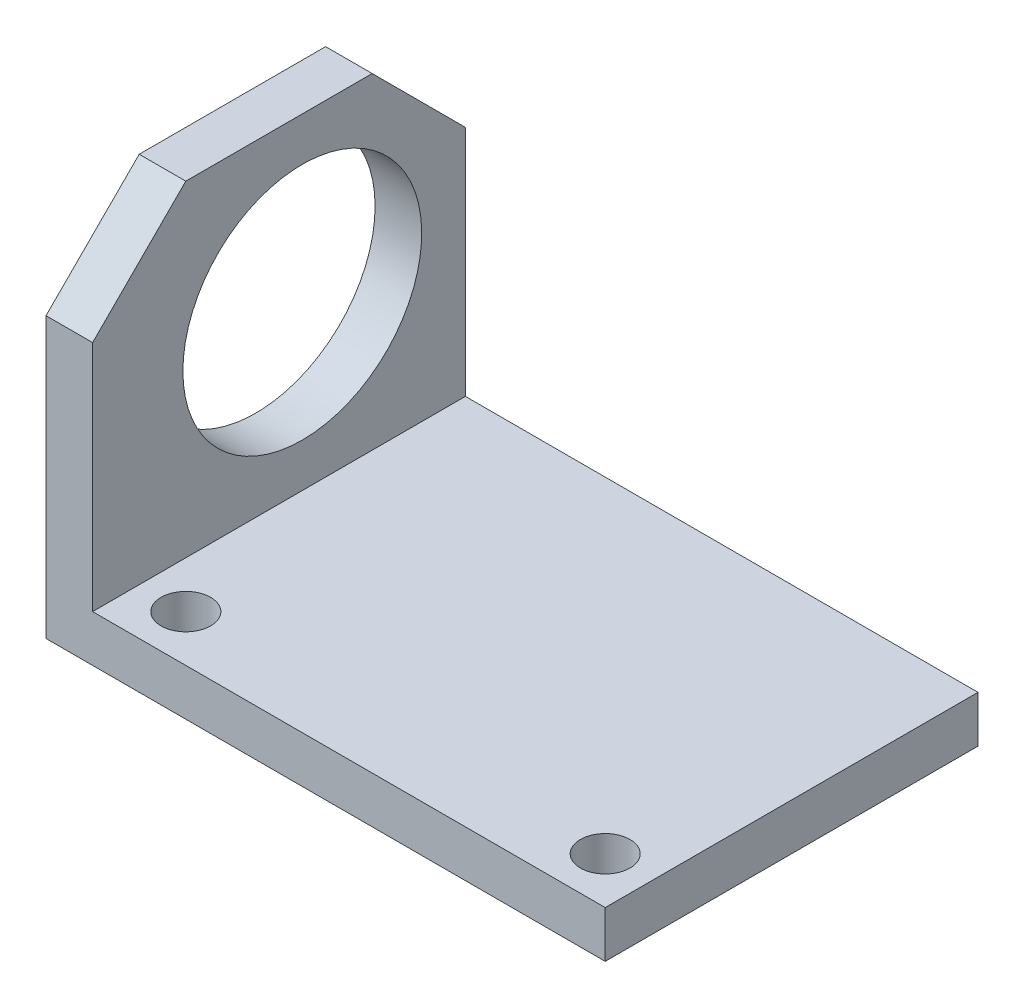
SolidWorks part; units mm, degrees
ref_plane "Front" through (0, 0, 0) normal (0, 0, 1) x (1, 0, 0)
ref_plane "Top" through (0, 0, 0) normal (0, 1, 0) x (1, 0, 0)
ref_plane "Right" through (0, 0, 0) normal (1, 0, 0) x (0, 0, -1)
sketch "Sketch1" plane through (0, 0, 0) normal (0, 0, 1) x (1, 0, 0)
  line L0 (0, 0) -> (76.2, 0)
  line L1 (50, 0) -> (-50, 0) construction
  line L2 (76.2, 0) -> (76.2, 6.35)
  line L3 (76.2, 6.35) -> (6.35, 6.35)
  line L4 (6.35, 6.35) -> (6.35, 50.8)
  line L5 (6.35, 50.8) -> (0, 50.8)
  line L6 (0, -50) -> (0, 50) construction
  line L7 (0, 50.8) -> (0, 0)
  dimension "D1" = 6.35
  dimension "D2" = 76.2
  dimension "D3" = 50.8
extrude "Boss-Extrude1" add sketch "Sketch1" along normal mid plane 50.8
sketch "Sketch2" plane through (0, 0, 0) normal (0, -1, 0) x (1, 0, 0)
  line L0 (76.2, 19.05) -> (69.85, 19.05) construction
  line L2 (69.85, 19.05) -> (12.7, 19.05) construction
  line L3 (76.2, 25.4) -> (76.2, -25.4) construction
  line L4 (0, 25.4) -> (76.2, 25.4) construction
  dimension "D1" = 57.15
  dimension "D2" = 6.35
  dimension "D3" = 6.35
hole_wizard "1/4 Clearance Hole1" positions "Sketch4" profile "Sketch3" hole size "1/4" standard "ANSI Inch" end condition through all
sketch "Sketch4" plane through (0, 0, 0) normal (0, -1, 0) x (-1, 0, 0)
  point P0 (-12.7, -19.05)
  point P3 (-69.85, -19.05)
sketch "Sketch3" plane through (12.7, 0, 19.05) normal (1, 0, 0) x (0, 0, -1)
  line L0 (0, 0) -> (0, 50.8)
  line L1 (0, 50.8) -> (3.3782, 50.8)
  line L2 (3.3782, 50.8) -> (3.3782, 0)
  line L5 (3.3782, 0) -> (0, 0)
  line L11 (0, -6.35) -> (0, 107.95) construction
  dimension "Thru Hole Dia." = 6.7564
  dimension "Thru Hole Depth" = 50.8
sketch "Sketch5" plane through (0, 0, 0) normal (-1, 0, 0) x (0, 0, 1)
  line L0 (-3.175, 0) -> (-3.175, 28.575) construction
  line L2 (-25.4, 50.8) -> (-25.4, 0) construction
  dimension "D1" = 28.575
  dimension "D2" = 22.225
hole_wizard "1-1/4 Clearance Hole1" positions "Sketch7" profile "Sketch6" hole size "1-1/4" standard "ANSI Inch" end condition through all
sketch "Sketch7" plane through (0, 0, 0) normal (-1, 0, 0) x (0, 0, 1)
  point P0 (-3.175, 28.575)
sketch "Sketch6" plane through (0, 28.575, -3.175) normal (0, 1, 0) x (0, 0, 1)
  line L0 (0, 0) -> (0, 76.2)
  line L1 (0, 76.2) -> (16.2712, 76.2)
  line L2 (16.2712, 76.2) -> (16.2712, 0)
  line L5 (16.2712, 0) -> (0, 0)
  line L11 (0, -6.35) -> (0, 107.95) construction
  dimension "Thru Hole Dia." = 32.5425
  dimension "Thru Hole Depth" = 76.2
chamfer "Chamfer1" distance 12.7 angle 45 2 edges at (3.175, 50.8, -25.4) (3.175, 50.8, 25.4)
